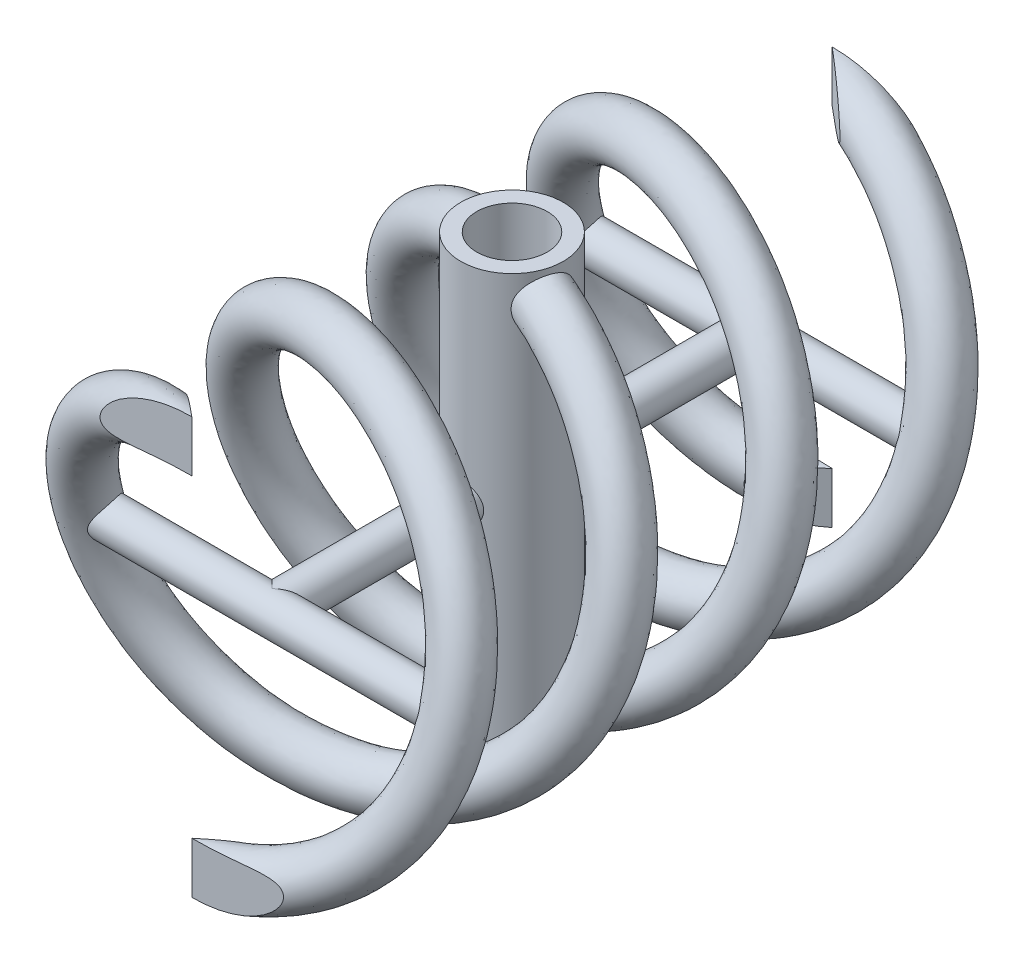
SolidWorks part; units mm, degrees
ref_plane "Front Plane" through (0, 0, 0) normal (0, 0, 1) x (1, 0, 0)
ref_plane "Top Plane" through (0, 0, 0) normal (0, 1, 0) x (1, 0, 0)
ref_plane "Right Plane" through (0, 0, 0) normal (1, 0, 0) x (0, 0, -1)
other "Configuration Table"
sketch "Sketch1" plane through (0, 0, 0) normal (0, 0, 1) x (1, 0, 0)
  circle A0 centre (0, 0) radius 2.85
curve "Helix/Spiral1" pitch 5 height 10 turns 2
sweep "Sweep1" add path "Helix/Spiral1" circular profile diameter 0.8 parameters "D3"=0.8
move or copy body "Body-Move/Copy1" bodies to move or copy 102 copy yes number of copies 1 rotation origin (0, 0, 0) rotation axis (0, 0, 1) rotation angle 180
sketch "Sketch13" plane through (0, 0, 0) normal (0, 0, 1) x (1, 0, 0)
  circle A0 centre (0, 0) radius 0.88
sketch "Sketch26" plane through (0, 0, 0) normal (1, 0, 0) x (0, 0, -1)
  circle A0 centre (-8.75, 0) radius 0.3
  circle A1 centre (-1.25, 0) radius 0.3
  spline S0 degree 3 poles (0, 2.85) (-0.1035, 2.85) (-0.3128, 2.7016) (-0.6249, 2.0677) (-0.9375, 1.119) (-1.25, 0) (-1.5625, -1.119) (-1.875, -2.0677) (-2.1875, -2.7016) (-2.5, -2.9242) (-2.8125, -2.7016) (-3.125, -2.0677) (-3.5417, -0.8028) (-3.9583, 0.8028) (-4.375, 2.0677) (-4.6875, 2.7016) (-5, 2.9242) (-5.3125, 2.7016) (-5.625, 2.0677) (-6.0417, 0.8028) (-6.4583, -0.8028) (-6.875, -2.0677) (-7.1875, -2.7016) (-7.5, -2.9242) (-7.8125, -2.7016) (-8.125, -2.0677) (-8.4375, -1.119) (-8.75, 0) (-9.0625, 1.119) (-9.3751, 2.0677) (-9.6872, 2.7016) (-9.8965, 2.85) (-10, 2.85) knots 0 0 0 0 0.03125 0.0625 0.09375 0.125 0.15625 0.1875 0.21875 0.25 0.28125 0.3125 0.34375 0.40625 0.4375 0.46875 0.5 0.53125 0.5625 0.59375 0.65625 0.6875 0.71875 0.75 0.78125 0.8125 0.84375 0.875 0.90625 0.9375 0.96875 1 1 1 1 construction
extrude "Boss-Extrude5" add sketch "Sketch26" along normal mid plane 6
sketch "Sketch31" plane through (0, 0, 0) normal (0, 1, 0) x (1, 0, 0)
  circle A0 centre (0, -5) radius 0.8
  spline S0 degree 3 poles (0, 0) (0.3708, -0.1035) (1.12, -0.3128) (2.0674, -0.6249) (2.7017, -0.9375) (2.9242, -1.25) (2.7016, -1.5625) (2.0677, -1.875) (0.8028, -2.2917) (-0.8028, -2.7083) (-2.0677, -3.125) (-2.7016, -3.4375) (-2.9242, -3.75) (-2.7016, -4.0625) (-2.0677, -4.375) (-0.8028, -4.7917) (0.8028, -5.2083) (2.0677, -5.625) (2.7016, -5.9375) (2.9242, -6.25) (2.7016, -6.5625) (2.0677, -6.875) (0.8028, -7.2917) (-0.8028, -7.7083) (-2.0677, -8.125) (-2.7016, -8.4375) (-2.9242, -8.75) (-2.7017, -9.0625) (-2.0674, -9.3751) (-1.12, -9.6872) (-0.3708, -9.8965) (0, -10) knots 0 0 0 0 0.03125 0.0625 0.09375 0.125 0.15625 0.1875 0.21875 0.28125 0.3125 0.34375 0.375 0.40625 0.4375 0.46875 0.53125 0.5625 0.59375 0.625 0.65625 0.6875 0.71875 0.78125 0.8125 0.84375 0.875 0.90625 0.9375 0.96875 1 1 1 1 construction
extrude "Boss-Extrude6" add sketch "Sketch31" along normal mid plane 6.5
sketch "Sketch14" plane through (0, 0, 0) normal (1, 0, 0) x (0, 0, -1)
  line L0 (-10, 0) -> (-10, 4.2029)
  line L2 (-10, 4.2029) -> (-11.2562, 4.2029)
  line L3 (-11.2562, 4.2029) -> (-11.2562, -3.5466)
  line L4 (-11.2562, -3.5466) -> (-10, -3.5466)
  line L5 (-10, -3.5466) -> (-10, 0)
  dimension "D1" = 10
extrude "Cut-Extrude1" cut sketch "Sketch14" against normal through all both and the other way through all
sketch "Sketch15" plane through (0, 0, 0) normal (1, 0, 0) x (0, 0, -1)
  line L0 (0, 0) -> (0, 4.5649)
  line L1 (0, 4.5649) -> (2.0707, 4.5649)
  line L2 (2.0707, 4.5649) -> (2.0707, -3.8182)
  line L3 (2.0707, -3.8182) -> (0, -3.8182)
  line L4 (0, -3.8182) -> (0, 0)
extrude "Cut-Extrude2" cut sketch "Sketch15" against normal through all both and the other way through all
ref_plane "Plane1" through (0, 3.25, 0) normal (0, 1, 0) x (1, 0, 0)
sketch "Sketch17" plane through (0, 3.25, 0) normal (0, 1, 0) x (1, 0, 0)
  line L0 (0, -10) -> (0.5721, -10)
  line L2 (0.5721, -8.8044) -> (0.5721, -10)
  line L3 (0, -10) -> (-1.4248, -8.8044)
  line L4 (-1.4248, -8.8044) -> (0.5721, -8.8044)
  line L5 (0, 0) -> (-0.5721, 0)
  line L6 (0, 0) -> (-1.4328, 0) construction
  line L7 (-0.5721, 0) -> (-0.5721, -1.1956)
  line L8 (-0.5721, -1.1956) -> (1.4248, -1.1956)
  line L9 (1.4248, -1.1956) -> (0, 0)
  line L10 (0, -10) -> (1.4328, -10) construction
  dimension "D1" = 40
  dimension "D2" = 1.86
  dimension "D3" = 40
  dimension "D4" = 1.86
  dimension "D5" = 0.5721
extrude "Cut-Extrude8" cut sketch "Sketch17" against normal blind 2 and the other way through all
ref_plane "Plane2" through (0, -3.25, 0) normal (0, 1, 0) x (1, 0, 0)
sketch "Sketch19" plane through (0, -3.25, 0) normal (0, 1, 0) x (1, 0, 0)
  line L0 (0, 0) -> (0.5164, 0)
  line L2 (0.5164, 0) -> (0.5164, -1.1956)
  line L3 (0, 0) -> (-1.4248, -1.1956)
  line L4 (-1.4248, -1.1956) -> (0.5164, -1.1956)
  line L5 (0, -10) -> (-0.358, -10)
  line L7 (-0.358, -10) -> (-0.373, -10)
  line L8 (-0.373, -10) -> (-0.373, -8.8044)
  line L9 (-0.373, -8.8044) -> (1.4248, -8.8044)
  line L10 (1.4248, -8.8044) -> (0, -10)
  line L11 (1.4328, 0) -> (0, 0) construction
  line L12 (-1.4328, -10) -> (0, -10) construction
  dimension "D1" = 40
  dimension "D2" = 1.86
  dimension "D3" = 40
  dimension "D4" = 1.86
extrude "Cut-Extrude10" cut sketch "Sketch19" along normal blind 2
sketch "Sketch21" plane through (0, 0, 0) normal (0, 0, 1) x (1, 0, 0)
  circle A0 centre (0, 0) radius 0.55
ref_plane "Plane3" through (0, 0, 5) normal (0, 0, 1) x (1, 0, 0)
sketch "Sketch35" plane through (0, 0, 5) normal (0, 0, 1) x (1, 0, 0)
  circle A0 centre (0, 0) radius 0.3
extrude "Boss-Extrude7" add sketch "Sketch35" along normal mid plane 7.5
sketch "Sketch33" plane through (0, 3.25, 0) normal (0, 1, 0) x (1, 0, 0)
  circle A0 centre (0, -5) radius 0.55
extrude "Cut-Extrude11" cut sketch "Sketch33" against normal blind 10
